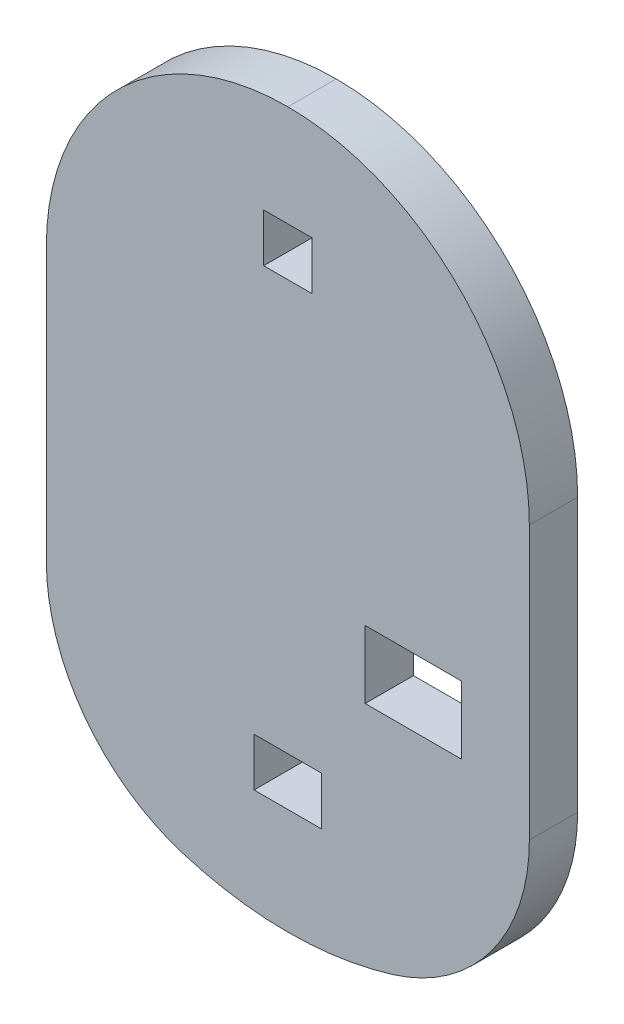
SolidWorks part; units mm, degrees
material "Acrylic (Medium-high impact)"
ref_plane "Front Plane" through (0, 0, 0) normal (0, 0, 1) x (1, 0, 0)
ref_plane "Top Plane" through (0, 0, 0) normal (0, 1, 0) x (1, 0, 0)
ref_plane "Right Plane" through (0, 0, 0) normal (1, 0, 0) x (0, 0, -1)
sketch "Sketch1" plane through (0, 0, 0) normal (0, 0, 1) x (1, 0, 0)
  circle A0 centre (0, 0) radius 37
  dimension "D1" = 74
extrude "Boss-Extrude1" add sketch "Sketch1" along normal blind 5
sketch "Sketch6" plane through (0, 0, 5) normal (0, 0, 1) x (1, 0, 0)
  line L0 (-25, 27.2764) -> (-25, -27.2764)
  line L1 (25, -27.2764) -> (25, 27.2764)
  arc A0 (25, -27.2764) -> (25, 27.2764) centre (0, 0) ccw
  circle A1 centre (0, 0) radius 37
  arc A2 (-25, 27.2764) -> (-25, -27.2764) centre (0, 0) ccw
  dimension "D2" = 25
  dimension "D3" = 50
  dimension "D1" = 0
extrude "Cut-Extrude3" cut sketch "Sketch6" against normal blind 10
fillet "Fillet2" radius 25 2 edges at (-25, 27.2764, 2.5) (25, 27.2764, 2.5)
fillet "Fillet3" radius 20 2 edges at (25, -27.2764, 2.5) (-25, -27.2764, 2.5)
sketch "Sketch7" plane through (0, 0, 5) normal (0, 0, 1) x (1, 0, 0)
  line L1 (-2.5, 26.5) -> (2.5, 26.5)
  line L2 (-2.5, 26.5) -> (-2.5, 21.5)
  line L3 (-2.5, 21.5) -> (2.5, 21.5)
  line L4 (2.5, 26.5) -> (2.5, 21.5)
  line L5 (-3.5, -21) -> (3.5, -21)
  line L6 (-3.5, -21) -> (-3.5, -26)
  line L7 (-3.5, -26) -> (3.5, -26)
  line L8 (3.5, -21) -> (3.5, -26)
  point P9 (0, 21.5)
  point P11 (0, -21)
  dimension "D1" = 10.5
  dimension "D2" = 42.5
  dimension "D3" = 5
  dimension "D4" = 7
  dimension "D5" = 5
extrude "Cut-Extrude4" cut sketch "Sketch7" against normal blind 10
sketch "Sketch2" plane through (0, 0, 5) normal (0, 0, 1) x (1, 0, 0)
  line L1 (-5, 26.5) -> (5, 26.5)
  line L2 (-5, 26.5) -> (-5, 21.5)
  line L3 (-5, 21.5) -> (5, 21.5)
  line L4 (5, 26.5) -> (5, 21.5)
  line L5 (-5, 26.5) -> (5, 21.5) construction
  line L6 (-5, 21.5) -> (5, 26.5) construction
  point P0 (0, 24)
  dimension "D1" = 5
  dimension "D2" = 26.5
  dimension "D3" = 10
extrude "Boss-Extrude2" [suppressed] add sketch "Sketch2" along normal blind 38
sketch "Sketch3" [suppressed] plane through (0, 26.5, 0) normal (0, 1, 0) x (1, 0, 0)
  line L0 (5, -5) -> (-5, -5) construction
  line L1 (5, -43) -> (-5, -43) construction
  circle A0 centre (0, -12) radius 0.5
  circle A1 centre (0, -14) radius 0.5
  circle A2 centre (0, -16) radius 0.5
  circle A3 centre (0, -18) radius 0.5
  circle A4 centre (0, -20) radius 0.5
  circle A5 centre (0, -22) radius 0.5
  circle A6 centre (0, -40.5) radius 0.5
  circle A7 centre (0, -38.5) radius 0.5
  circle A8 centre (0, -36.5) radius 0.5
  circle A9 centre (0, -34.5) radius 0.5
  circle A10 centre (0, -32.5) radius 0.5
  circle A11 centre (0, -30.5) radius 0.5
  point P20 (0, -43)
  dimension "D2" = 1
  dimension "D5" = 8.5
  dimension "D6" = 2
  dimension "D1" = 7
  dimension "D7" = 2
  dimension "D3" = 6
  dimension "D4" = 6
extrude "Cut-Extrude1" [suppressed] cut sketch "Sketch3" against normal blind 5
sketch "Sketch4" [suppressed] plane through (0, 0, 5) normal (0, 0, 1) x (1, 0, 0)
  line L1 (-7.5, -20.5) -> (7.5, -20.5)
  line L2 (-7.5, -20.5) -> (-7.5, -25.5)
  line L3 (-7.5, -25.5) -> (7.5, -25.5)
  line L4 (7.5, -20.5) -> (7.5, -25.5)
  line L5 (-7.5, -20.5) -> (7.5, -25.5) construction
  line L6 (-7.5, -25.5) -> (7.5, -20.5) construction
  line L7 (-5, 21.5) -> (5, 21.5) construction
  point P0 (0, -23)
  dimension "D1" = 42
  dimension "D2" = 15
  dimension "D3" = 5
extrude "Boss-Extrude3" [suppressed] add sketch "Sketch4" along normal blind 32
sketch "Sketch5" [suppressed] plane through (0, -20.5, 0) normal (0, 1, 0) x (1, 0, 0)
  line L0 (-7.5, -5) -> (7.5, -5) construction
  circle A0 centre (0, -26.25) radius 3.8
  dimension "D1" = 21.25
  dimension "D2" = 7.6
extrude "Cut-Extrude2" [suppressed] cut sketch "Sketch5" against normal blind 28
fillet "Fillet4" [suppressed] radius 0.5
sketch "Sketch8" plane through (0, 0, 5) normal (0, 0, 1) x (1, 0, 0)
  line L0 (25, 12) -> (25, -16.2481) construction
  line L1 (8, -5.5) -> (18, -5.5)
  line L2 (8, -5.5) -> (8, -12.5)
  line L3 (8, -12.5) -> (18, -12.5)
  line L4 (18, -5.5) -> (18, -12.5)
  line L5 (3.5, -21) -> (-3.5, -21) construction
  dimension "D1" = 10
  dimension "D2" = 7
  dimension "D3" = 7
  dimension "D4" = 8.5
extrude "Cut-Extrude5" cut sketch "Sketch8" against normal blind 10
